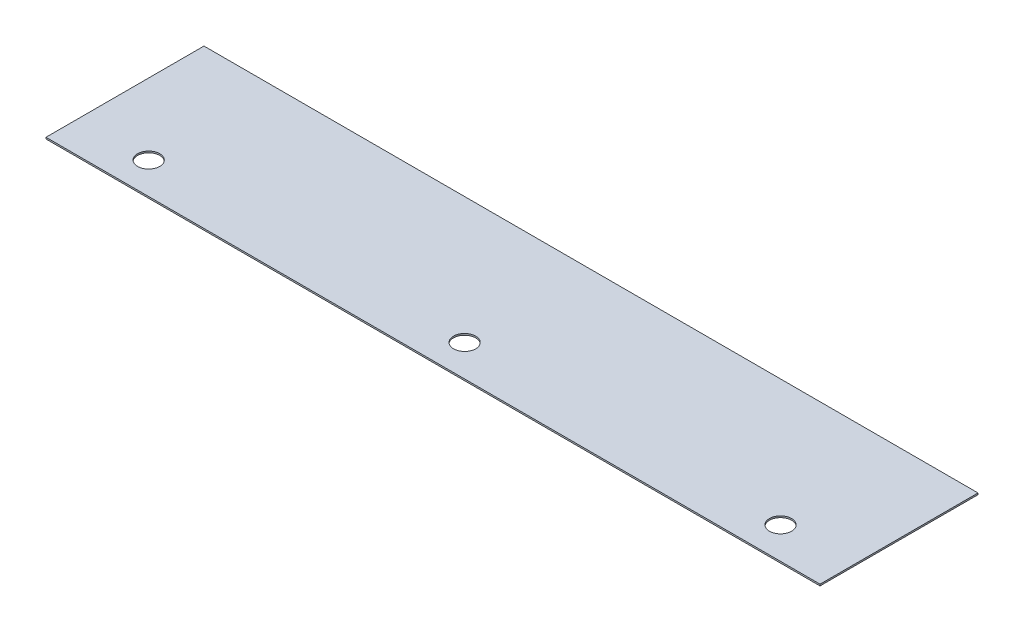
SolidWorks part; units mm, degrees
note: The reader was unsure of these and kept them because the rebuilt part matched: thickness of "Base-Flange1", "Sheet-Metal1", "Sheet-Metal2", "Sheet-Metal3", "Sheet-Metal4".
material "AISI 304"
ref_plane "Front Plane" through (0, 0, 0) normal (0, 0, 1) x (1, 0, 0)
ref_plane "Top Plane" through (0, 0, 0) normal (0, 1, 0) x (1, 0, 0)
ref_plane "Right Plane" through (0, 0, 0) normal (1, 0, 0) x (0, 0, -1)
sketch "Sketch1" plane through (0, 0, 0) normal (0, 1, 0) x (1, 0, 0)
  line L1 (-122.5, -25) -> (122.5, -25)
  line L2 (-122.5, -25) -> (-122.5, 25)
  line L3 (-122.5, 25) -> (122.5, 25)
  line L4 (122.5, -25) -> (122.5, 25)
  line L5 (-122.5, -25) -> (122.5, 25) construction
  line L6 (-122.5, 25) -> (122.5, -25) construction
  point P0 (0, 0)
  dimension "D1" = 50
  dimension "D2" = 245
base flange "Base-Flange1" sketch "Sketch1" thickness 0.5 reverse thickness direction no parameters "D1"=0
sketch "Sketch6" plane through (0, 0, 0) normal (0, 1, 0) x (1, 0, 0)
  line L0 (-122.5, -25) -> (122.5, -25) construction
  circle A0 centre (0, -15) radius 3.5
  dimension "D1" = 7
  dimension "D2" = 10
extrude "Cut-Extrude1" cut sketch "Sketch6" against normal blind 10 normal cut yes
pattern_linear "LPattern1" count 6 spacing 146 along (-1, 0, 0) count 6 spacing 146 along (1, 0, 0) of "Cut-Extrude1"
pattern_linear "LPattern2" count 2 spacing 100 along (-1, 0, 0) count 2 spacing 100 along (1, 0, 0) of "Cut-Extrude1"
sketch "Bend-Lines1" [suppressed] plane through (0, 0, 0) normal (0, 1, 0) x (1, 0, 0)
sketch "Bounding-Box1" [suppressed] plane through (0, 0, 0) normal (0, 1, 0) x (1, 0, 0)
sheet metal parameters "Sheet-Metal1" thickness 0.5 parameters "D1"=0
flat pattern "Flat-Pattern1" [suppressed]
sketch "Bend-Lines2" plane through (0, 0, 0) normal (0, 1, 0) x (1, 0, 0)
sketch3d "Bounding-Box2" [suppressed]
  line L0 (-790, 10, 0) -> (790, 10, 0) construction
  line L1 (-790, -10, 0) -> (790, -10, 0) construction
  line L2 (-790, 10, 0) -> (-790, -10, 0) construction
  line L3 (790, 10, 0) -> (790, -10, 0) construction
sheet metal parameters "Sheet-Metal2" thickness 0.5 parameters "D1"=0, "D7"=2
flat pattern "Flat-Pattern1"
sketch "Bend-Lines2" plane through (0, 0, 0) normal (0, 1, 0) x (1, 0, 0)
sketch3d "Bounding-Box2" [suppressed]
  line L0 (790, 10, 0) -> (-790, 10, 0) construction
  line L1 (790, -10, 0) -> (-790, -10, 0) construction
  line L2 (790, 10, 0) -> (790, -10, 0) construction
  line L3 (-790, 10, 0) -> (-790, -10, 0) construction
sheet metal parameters "Sheet-Metal3" thickness 0.5 parameters "D1"=0, "D7"=2
flat pattern "Flat-Pattern1"
sketch "Bend-Lines2" plane through (0, 0, 0) normal (0, 1, 0) x (1, 0, 0)
sketch3d "Bounding-Box2" [suppressed]
  line L0 (122.5, 30, 0) -> (-122.5, 30, 0) construction
  line L1 (122.5, -30, 0) -> (-122.5, -30, 0) construction
  line L2 (122.5, 30, 0) -> (122.5, -30, 0) construction
  line L3 (-122.5, 30, 0) -> (-122.5, -30, 0) construction
sheet metal parameters "Sheet-Metal4" thickness 0.5 parameters "D1"=0, "D7"=2
flat pattern "Flat-Pattern1"
sketch "Bend-Lines2" plane through (0, 0, 0) normal (0, 1, 0) x (1, 0, 0)
sketch3d "Bounding-Box2" [suppressed]
  line L0 (122.5, 25, 0) -> (-122.5, 25, 0) construction
  line L1 (122.5, -25, 0) -> (-122.5, -25, 0) construction
  line L2 (122.5, 25, 0) -> (122.5, -25, 0) construction
  line L3 (-122.5, 25, 0) -> (-122.5, -25, 0) construction
